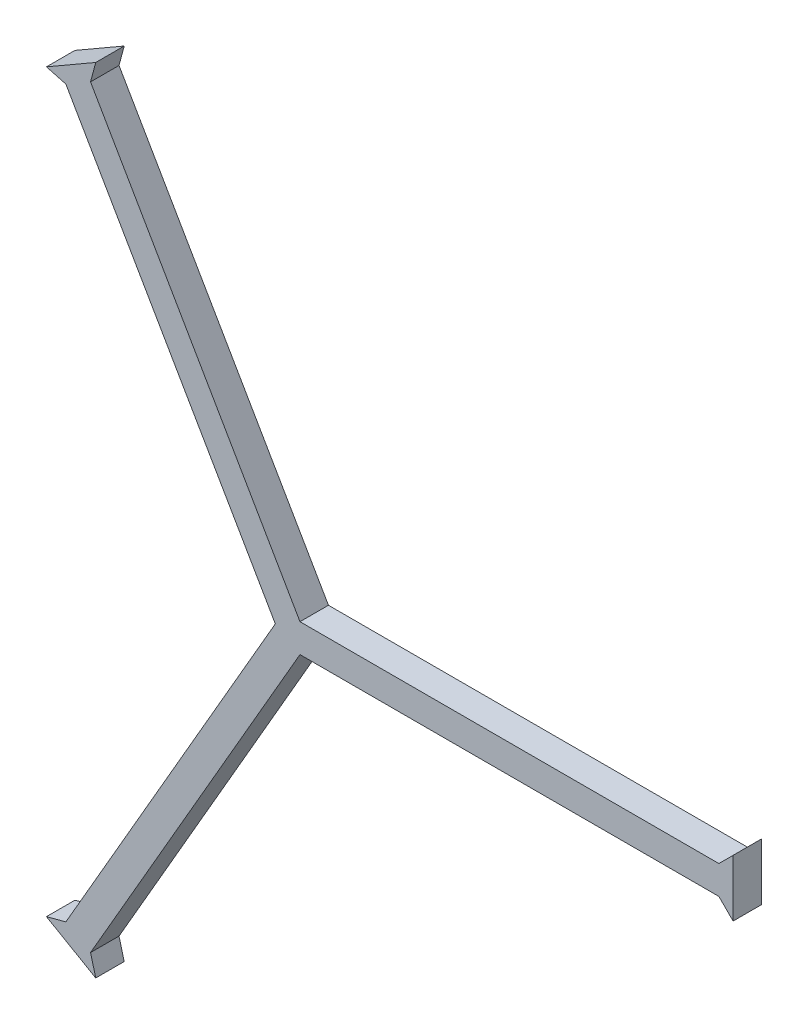
SolidWorks part; units mm, degrees
ref_plane "Front Plane" through (0, 0, 0) normal (0, 0, 1) x (1, 0, 0)
ref_plane "Top Plane" through (0, 0, 0) normal (0, 1, 0) x (1, 0, 0)
ref_plane "Right Plane" through (0, 0, 0) normal (1, 0, 0) x (0, 0, -1)
sketch "Sketch1" plane through (0, 0, 0) normal (0, 0, 1) x (1, 0, 0)
  line L0 (0, 0) -> (165, 0) construction
  line L1 (155, 10) -> (150, 5)
  line L2 (150, 5) -> (0, 5)
  line L3 (155, 10) -> (155, -10)
  line L4 (150, -5) -> (0, -5)
  line L5 (155, -10) -> (150, -5)
  line L6 (0, 5) -> (0, -5)
  circle A0 centre (0, 0) radius 165 construction
  point P11 (155, 0)
  dimension "D1" = 330
  dimension "D2" = 45
  dimension "D3" = 20
  dimension "D4" = 10
  dimension "D5" = 10
extrude "Boss-Extrude1" add sketch "Sketch1" along normal blind 10
ref_axis "Axis1" through (0, 0, 0) along (0, 0, 1)
pattern_circular "CirPattern1" count 3 over 360 about axis through (0, 0, 0) along (0, 0, 1) of "Boss-Extrude1"
